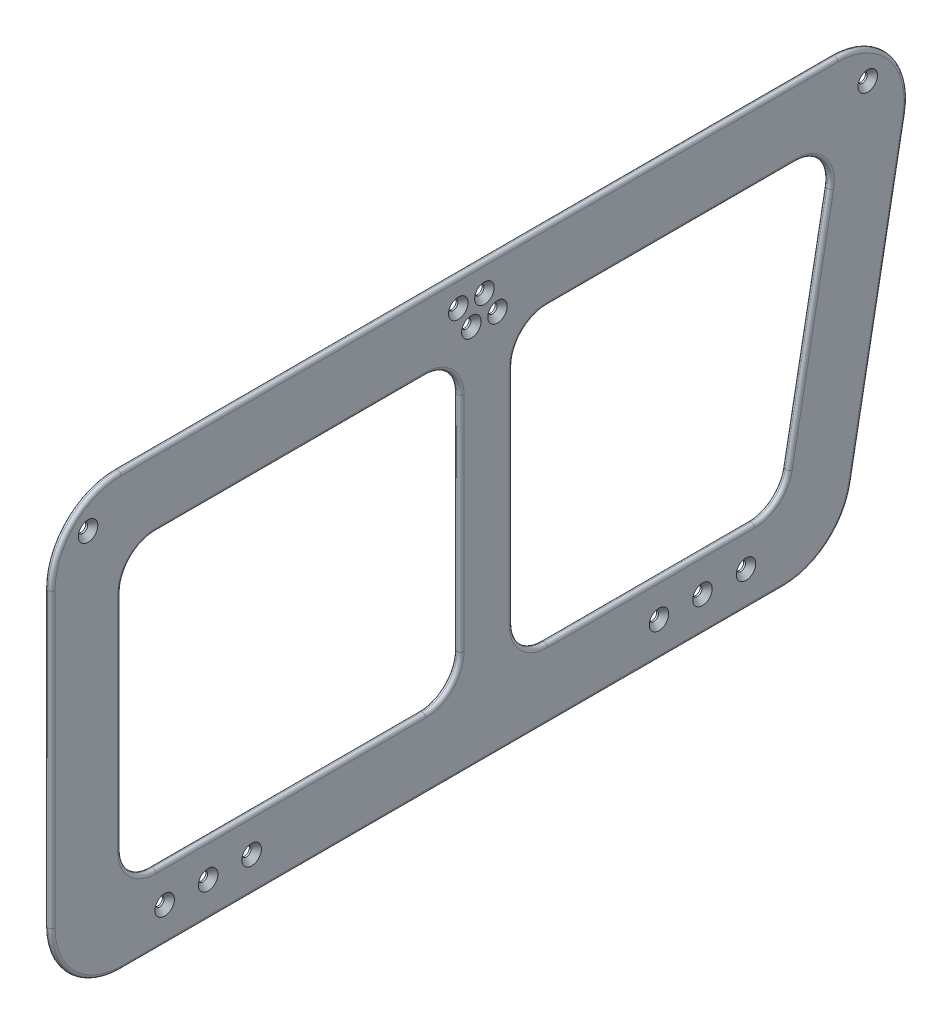
SolidWorks part; units mm, degrees
material "PVC Rígido"
ref_plane "Alzado" through (0, 0, 0) normal (0, 0, 1) x (1, 0, 0)
ref_plane "Planta" through (0, 0, 0) normal (0, 1, 0) x (1, 0, 0)
ref_plane "Vista lateral" through (0, 0, 0) normal (1, 0, 0) x (0, 0, -1)
sketch "Croquis1" plane through (0, 0, 0) normal (1, 0, 0) x (0, 0, -1)
  line L0 (0, 0) -> (0, 248) construction
  line L1 (250, 0) -> (250, 248) construction
  line L2 (-250, 0) -> (-250, 248)
  line L3 (-250, 248) -> (250, 248)
  line L4 (203.83, 0) -> (250, 248)
  line L5 (-250, 0) -> (203.83, 0)
  line L6 (-250, 0) -> (250, 0) construction
  line L8 (170.5895, 40) -> (201.8659, 208)
  line L9 (-15, 208) -> (-15, 40)
  line L10 (-210, 40) -> (-210, 208)
  line L11 (15, 208) -> (15, 40)
  line L12 (15, 208) -> (201.8659, 208)
  line L13 (15, 40) -> (170.5895, 40)
  line L15 (250, 0) -> (-250, 0) construction
  line L16 (-210, 208) -> (-15, 208)
  line L17 (-210, 208) -> (201.8659, 208) construction
  line L18 (-210, 40) -> (-15, 40)
  line L19 (-210, 40) -> (170.5895, 40) construction
  line L21 (-210, 40) -> (-210, 208) construction
  line L26 (170.5895, 40) -> (201.8659, 208) construction
  point P16 (15, 124)
  dimension "D1" = 500
  dimension "D2" = 248
  dimension "D3" = 453.83
  dimension "D4" = 40
  dimension "D5" = 15
  dimension "D6" = 15
  dimension "D7" = 79.454
extrude "Saliente-Extruir1" add sketch "Croquis1" along normal mid plane 4
fillet "Redondeo1" radius 40 4 edges at (0, 0, 250) (0, 0, -203.83) (0, 248, -250) (0, 248, 250)
fillet "Redondeo2" radius 20 8 edges at (0, 40, 210) (0, 40, -170.5895) (0, 208, -201.8659) (0, 208, 15) (0, 40, 15) (0, 40, -15) (0, 208, -15) (0, 208, 210)
sketch "Croquis16" plane through (2, 0, 0) normal (1, 0, 0) x (0, 0, -1)
  line L0 (-160, 65.3788) -> (-160, -35.3668) construction
  line L1 (-135, 55.4734) -> (-135, -11.792) construction
  line L2 (-210, 0) -> (170.5895, 0) construction
  point P6 (-135, 20)
  point P7 (-185, 20)
  point P8 (-160, 20)
  dimension "D1" = 185
  dimension "D2" = 25
  dimension "D5" = 20
sketch "Croquis6" plane through (2, 0, 0) normal (1, 0, 0) x (0, 0, -1)
  line L0 (-8.75, 219.5048) -> (6.25, 219.5048) construction
  line L1 (-250, 208) -> (-250, 40) construction
  line L2 (-8.75, 219.5048) -> (-16.25, 232.4952) construction
  line L3 (-16.25, 232.4952) -> (-1.25, 232.4952) construction
  line L4 (-1.25, 232.4952) -> (-8.75, 219.5048) construction
  line L5 (-12.5, 226) -> (-1.25, 232.4952) construction
  line L6 (6.25, 219.5048) -> (-16.25, 232.4952) construction
  line L7 (-5, 40) -> (-5, 244.7997) construction
  line L8 (-190, 40) -> (-35, 40) construction
  line L9 (201.8659, 248) -> (-210, 248) construction
  line L10 (6.25, 219.5048) -> (-1.25, 232.4952) construction
  line L11 (25.2993, 226) -> (-50.3931, 226) construction
  point P1 (-5, 226)
  point P12 (-8.75, 228.1651)
  dimension "D1" = 15
  dimension "D2" = 245
  dimension "D3" = 22
sketch "Croquis19" plane through (2, 0, 0) normal (1, 0, 0) x (0, 0, -1)
  line L0 (124.0546, 54.2009) -> (124.0546, -18.1862) construction
  line L1 (99.0546, 50.5291) -> (99.0546, -18.1862) construction
  line L3 (-210, 0) -> (170.5895, 0) construction
  point P4 (149.0546, 20)
  point P6 (99.0546, 20)
  point P7 (124.0546, 20)
  dimension "D1" = 149.0546
  dimension "D2" = 25
  dimension "D3" = 25
  dimension "D4" = 20
sketch "Croquis11" plane through (2, 0, 0) normal (1, 0, 0) x (0, 0, -1)
  line L0 (-5, 242.0188) -> (-5, -27.147) construction
  line L1 (201.8659, 248) -> (-210, 248) construction
  line L2 (-250, 208) -> (-250, 40) construction
  circle A0 centre (-229, 228) radius 10
  circle A1 centre (219, 228) radius 10
  dimension "D5" = 20
  dimension "D1" = 224
  dimension "D2" = 224
  dimension "D3" = 20
  dimension "D4" = 21
hole_wizard "Refrentado para tornillo tapón con cabeza plana de clavija de M51" positions "Croquis12" profile "Croquis14" countersink size "M5" standard "Ansi Metric" end condition through all
sketch "Croquis12" plane through (2, 0, 0) normal (1, 0, 0) x (0, 0, -1)
  point P0 (-229, 228)
  point P3 (219, 228)
  point P6 (149.0546, 20)
  point P9 (124.0546, 20)
  point P12 (99.0546, 20)
  point P15 (-185, 20)
  point P18 (-160, 20)
  point P21 (-135, 20)
  point P24 (-1.25, 232.4952)
  point P27 (-16.25, 232.4952)
  point P30 (-8.75, 219.5048)
  point P33 (6.25, 219.5048)
sketch "Croquis14" plane through (2, 228, 229) normal (0, 1, 0) x (0, 0, -1)
  line L0 (0, 0) -> (0, 4)
  line L1 (0, 4) -> (2.65, 4)
  line L2 (2.65, 4) -> (2.65, 2.95)
  line L3 (2.65, 2.95) -> (5.6, 0)
  line L5 (5.6, 0) -> (0, 0)
  line L6 (-2.65, 2.95) -> (-5.6, 0) construction
  line L11 (0, -6.35) -> (0, 107.95) construction
  dimension "Diámetro de taladro hasta el siguiente" = 5.3
  dimension "Profundidad de taladro hasta el siguiente" = 4
  dimension "Diámetro de avellanado cercano" = 11.2
  dimension "Ángulo de avellanado cercano" = 90
ref_plane "Plano1" through (-101.0445, 0, 0) normal (1, 0, 0) x (0, 0, -1)
mirror "Simetría2" [suppressed] about plane through (-101.0445, 0, 0) normal (1, 0, 0) of bodies 106 104
delete or keep bodies "Sólido-Eliminar/Conservar 1" [suppressed] type keep bodies bodies 105
fillet "Redondeo3" radius 2 48 edges at (-2, 45.8579, -20.8579) (-2, 124, -15) (-2, 202.1421, -20.8579) (-2, 208, -106.3995) (-2, 200.7826, -193.1809) (-2, 120.3395, -185.5463) (-2, 44.618, -166.7519) (-2, 45.8579, 204.1421) (-2, 124, 210) (-2, 202.1421, 204.1421) (-2, 208, 112.5) (-2, 202.1421, 20.8579) (-2, 124, 15) (-2, 45.8579, 20.8579) (2, 45.8579, -20.8579) (2, 124, -15) (2, 202.1421, -20.8579) (2, 208, -106.3995) (2, 200.7826, -193.1809) (2, 120.3395, -185.5463) (2, 44.618, -166.7519) (2, 202.1421, 20.8579) (2, 124, 15) (2, 45.8579, 20.8579) (2, 40, 112.5) (2, 45.8579, 204.1421) (2, 124, 210) (2, 202.1421, 204.1421) (-2, 40, -94.4846) (-2, 40, 112.5) (2, 40, -94.4846) (2, 208, 112.5) (-2, 233.5652, -232.6299) (-2, 116.679, -225.5521) (-2, 9.2361, -196.1547) (-2, 0, 19.7053) (-2, 11.7157, 238.2843) (-2, 124, 250) (-2, 236.2843, 238.2843) (2, 233.5652, -232.6299) (2, 116.679, -225.5521) (2, 9.2361, -196.1547) (2, 0, 19.7053) (2, 11.7157, 238.2843) (2, 124, 250) (2, 236.2843, 238.2843) (-2, 248, 4.067) (2, 248, 4.067)
fillet "Redondeo4" [suppressed] radius 2
sketch "Croquis8" [suppressed] plane through (-199.589, 0, 0) normal (1, 0, 0) x (0, 0, -1)
  line L0 (-250, 40) -> (-250, 160) construction
  line L1 (-210, 200) -> (199.7131, 200) construction
  line L4 (-5, 242.0188) -> (-5, -27.147) construction
  circle A0 centre (-229, 180) radius 10
  arc A1 (238.6879, 151.002) -> (199.7131, 200) centre (199.7131, 160) ccw construction
  circle A2 centre (219, 180) radius 10
  dimension "D1" = 21
  dimension "D3" = 20
  dimension "D5" = 204.7131
  dimension "D2" = 20
  dimension "D4" = 245
fillet "Redondeo5" [suppressed] radius 2
